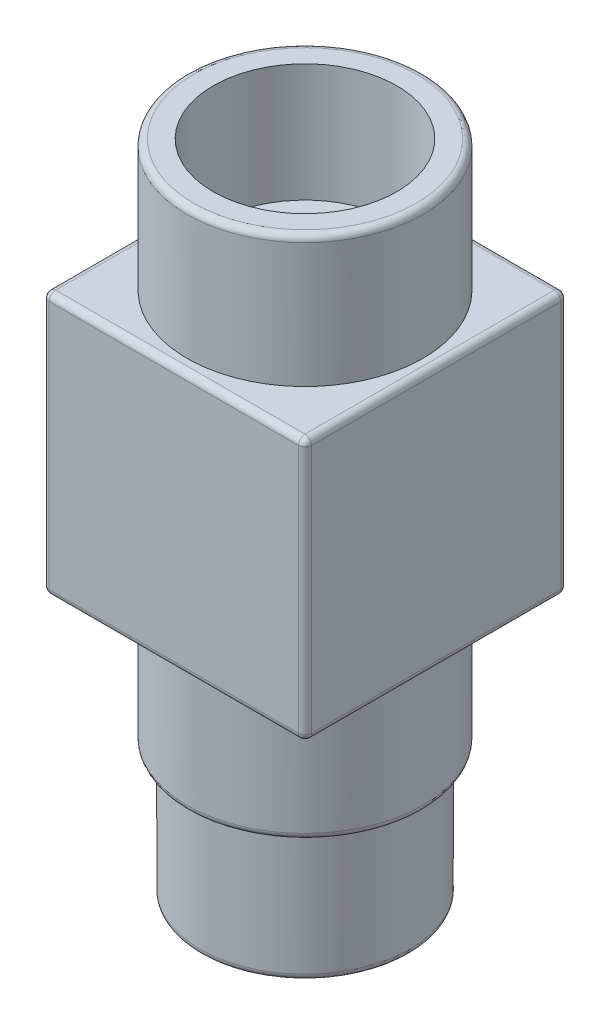
SolidWorks part; units mm, degrees
ref_plane "Alzado" through (0, 0, 0) normal (0, 0, 1) x (1, 0, 0)
ref_plane "Planta" through (0, 0, 0) normal (0, 1, 0) x (1, 0, 0)
ref_plane "Vista lateral" through (0, 0, 0) normal (1, 0, 0) x (0, 0, -1)
sketch "Croquis1" plane through (0, 0, 0) normal (0, 1, 0) x (1, 0, 0)
  line L1 (-20, -20) -> (20, -20)
  line L2 (-20, -20) -> (-20, 20)
  line L3 (-20, 20) -> (20, 20)
  line L4 (20, -20) -> (20, 20)
  line L5 (-20, -20) -> (20, 20) construction
  line L6 (-20, 20) -> (20, -20) construction
  point P0 (0, 0)
  dimension "D1" = 40
  dimension "D2" = 40
extrude "Saliente-Extruir2" add sketch "Croquis1" along normal mid plane 40
sketch "Croquis4" plane through (0, 0, 0) normal (0, 1, 0) x (1, 0, 0)
  circle A0 centre (0, 0) radius 18
  dimension "D1" = 36
extrude "Saliente-Extruir3" add sketch "Croquis4" along normal mid plane 80
fillet "Redondeo1" radius 1 10 edges at (0, -20, -20) (-20, -20, 0) (0, -20, 20) (20, -20, 0) (0, -40, 18) (0, 20, -20) (20, 20, 0) (0, 20, 20) (-20, 20, 0) (0, 40, 18)
sketch "Croquis5" plane through (0, -40, 0) normal (0, -1, 0) x (1, 0, 0)
  circle A0 centre (0, 0) radius 16
  dimension "D1" = 32
extrude "Saliente-Extruir4" add sketch "Croquis5" along normal blind 20
fillet "Redondeo2" radius 1 1 edges at (0, -60, -16)
sketch "Croquis6" plane through (0, 40, 0) normal (0, 1, 0) x (1, 0, 0)
  circle A0 centre (0, 0) radius 14
  dimension "D1" = 28
extrude "Cortar-Extruir1" cut sketch "Croquis6" against normal blind 18
sketch "Croquis7" plane through (0, -60, 0) normal (0, -1, 0) x (1, 0, 0)
  circle A0 centre (0, 0) radius 10
  dimension "25" = 20
extrude "Cortar-Extruir3" cut sketch "Croquis7" against normal through all
sketch "Croquis8" plane through (-20, 0, 0) normal (-1, 0, 0) x (0, 0, 1)
  circle A0 centre (0, 0) radius 9.5
  dimension "D1" = 19
extrude "Cortar-Extruir4" cut sketch "Croquis8" against normal blind 18
fillet "Redondeo3" radius 1 12 edges at (19.7071, 19.7071, 19.7071) (19.7071, -19.7071, 19.7071) (-19.7071, 19.7071, 19.7071) (-19.7071, -19.7071, 19.7071) (-19.7071, 19.7071, -19.7071) (-19.7071, -19.7071, -19.7071) (19.7071, 19.7071, -19.7071) (19.7071, -19.7071, -19.7071) (20, 0, 20) (-20, 0, 20) (-20, 0, -20) (20, 0, -20)
